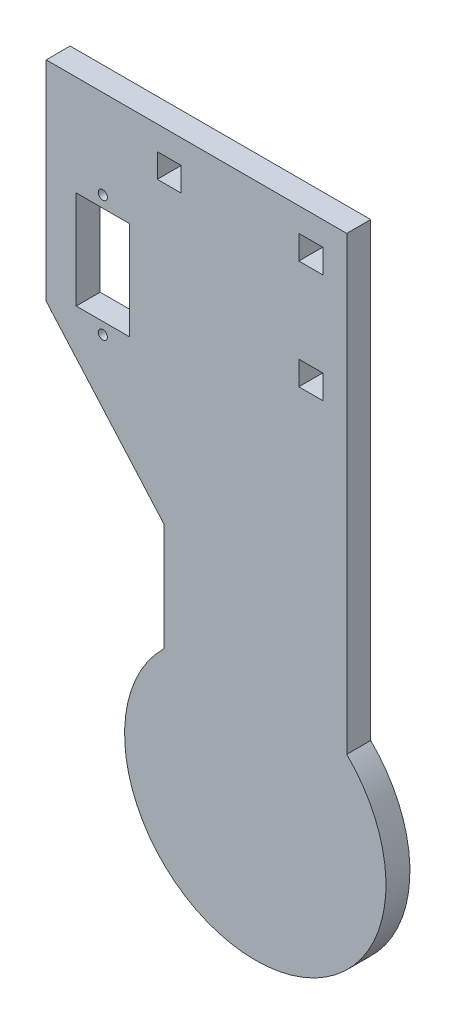
SolidWorks part; units mm, degrees
material "ﾁｰｸ材"
ref_plane "正面" through (0, 0, 0) normal (0, 0, 1) x (1, 0, 0)
ref_plane "平面" through (0, 0, 0) normal (0, 1, 0) x (1, 0, 0)
ref_plane "右側面" through (0, 0, 0) normal (1, 0, 0) x (0, 0, -1)
sketch "ｽｹｯﾁ1" plane through (0, 0, 0) normal (0, 0, 1) x (1, 0, 0)
  line L0 (21, 125) -> (-48, 125)
  line L1 (-21, 46.2619) -> (-21, 21.4243)
  line L2 (21, 125) -> (21, 21.4243)
  line L4 (-48, 125) -> (-48, 77)
  line L5 (-48, 77) -> (-21, 46.2619)
  arc A0 (-21, 21.4243) -> (21, 21.4243) centre (0, 0) ccw
  point P9 (-49, 120)
  point P10 (-49, 118.7599)
  dimension "D1" = 60
  dimension "D2" = 125
  dimension "D3" = 21
  dimension "D4" = 69
  dimension "D5" = 48
extrude "ﾎﾞｽ - 押し出し1" add sketch "ｽｹｯﾁ1" along normal blind 5.5
sketch "ｽｹｯﾁ2" plane through (0, 0, 5.5) normal (0, 0, 1) x (1, 0, 0)
  line L0 (21, 125) -> (-48, 125) construction
  line L1 (-28.9, 79.5) -> (-41.1, 79.5)
  line L2 (-28.9, 79.5) -> (-28.9, 102)
  line L3 (-28.9, 102) -> (-41.1, 102)
  line L4 (-41.1, 79.5) -> (-41.1, 102)
  line L5 (-28.9, 79.5) -> (-41.1, 102) construction
  line L6 (-28.9, 102) -> (-41.1, 79.5) construction
  point P0 (-35, 90.75)
  dimension "D1" = 12.2
  dimension "D2" = 22.5
  dimension "D3" = 35
  dimension "D4" = 23
extrude "ｶｯﾄ - 押し出し1" cut sketch "ｽｹｯﾁ2" against normal through all
sketch "ｽｹｯﾁ3" plane through (0, 0, 5.5) normal (0, 0, 1) x (1, 0, 0)
  line L0 (0, 0) -> (0, 22.4882) construction
sketch "ｽｹｯﾁ4" plane through (0, 0, 5.5) normal (0, 0, 1) x (1, 0, 0)
  line L0 (21, 125) -> (-48, 125) construction
  line L1 (15.5, 114) -> (10, 114)
  line L2 (15.5, 114) -> (15.5, 119.5)
  line L3 (15.5, 119.5) -> (10, 119.5)
  line L4 (10, 114) -> (10, 119.5)
  line L5 (15.5, 114) -> (10, 119.5) construction
  line L6 (15.5, 119.5) -> (10, 114) construction
  line L7 (0, 0) -> (0, 22.4882) construction
  line L8 (-17, 114) -> (-22.5, 114)
  line L9 (-17, 114) -> (-17, 119.5)
  line L10 (-17, 119.5) -> (-22.5, 119.5)
  line L11 (-22.5, 114) -> (-22.5, 119.5)
  line L12 (-17, 114) -> (-22.5, 119.5) construction
  line L13 (-17, 119.5) -> (-22.5, 114) construction
  line L14 (-28.9, 102) -> (-41.1, 102) construction
  line L15 (15.5, 89) -> (10, 89)
  line L16 (15.5, 89) -> (15.5, 94.5)
  line L17 (15.5, 94.5) -> (10, 94.5)
  line L18 (10, 89) -> (10, 94.5)
  line L19 (15.5, 89) -> (10, 94.5) construction
  line L20 (15.5, 94.5) -> (10, 89) construction
  line L21 (-41.1, 79.5) -> (-28.9, 79.5) construction
  circle A0 centre (-35, 104.65) radius 1.05
  circle A1 centre (-35, 76.85) radius 1.05
  point P0 (12.75, 116.75)
  point P9 (-19.75, 116.75)
  point P14 (12.75, 91.75)
  point P23 (0, 0)
  point P28 (-35, 79.5)
  dimension "D11" = 2.1
  dimension "D1" = 5.5
  dimension "D2" = 5.5
  dimension "D3" = 5.5
  dimension "D4" = 10
  dimension "D5" = 5.5
  dimension "D6" = 5.5
  dimension "D7" = 27
  dimension "D8" = 5.5
  dimension "D9" = 5.5
  dimension "D10" = 25
  dimension "D12" = 2.65
  dimension "D13" = 2.65
extrude "ｶｯﾄ - 押し出し2" cut sketch "ｽｹｯﾁ4" against normal through all
